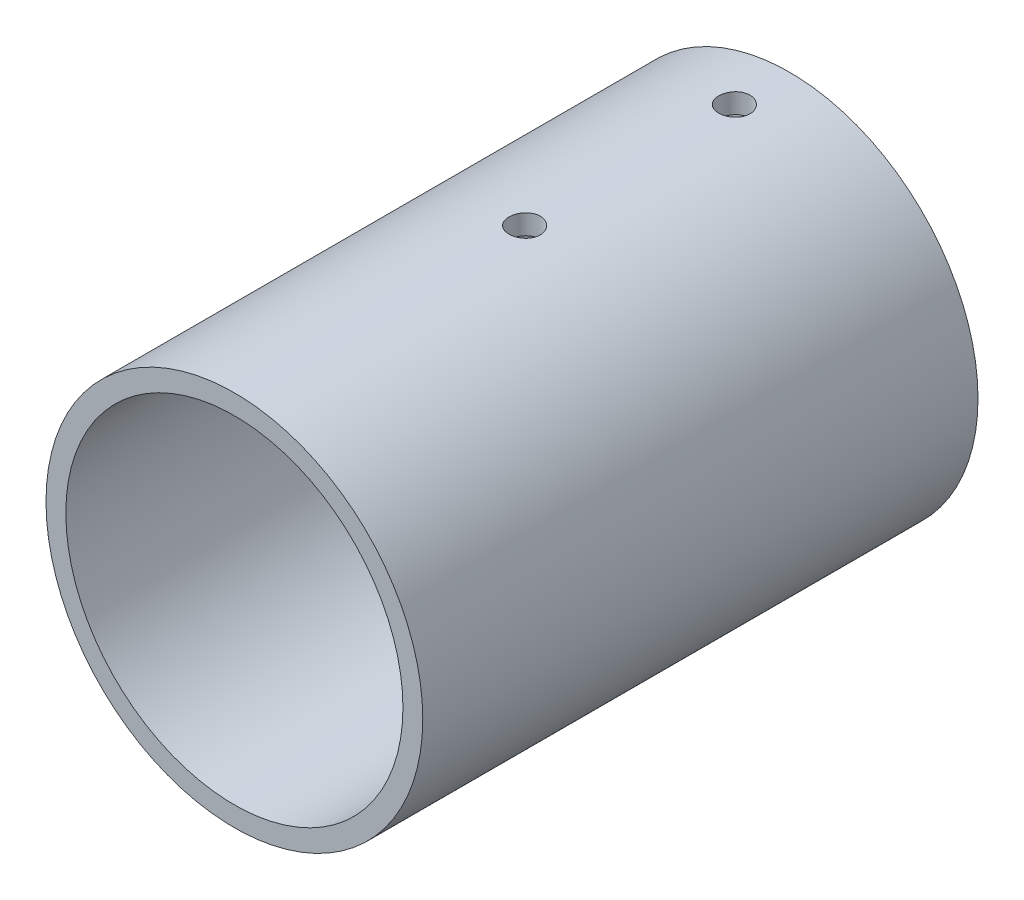
SolidWorks part; units mm, degrees
ref_plane "Front Plane" through (0, 0, 0) normal (0, 0, 1) x (1, 0, 0)
ref_plane "Top Plane" through (0, 0, 0) normal (0, 1, 0) x (1, 0, 0)
ref_plane "Right Plane" through (0, 0, 0) normal (1, 0, 0) x (0, 0, -1)
sketch "Sketch1" plane through (0, 0, 0) normal (0, 0, 1) x (1, 0, 0)
  circle A0 centre (0, 0) radius 60.325
  dimension "D1" = 120.65
extrude "Boss-Extrude1" add sketch "Sketch1" along normal blind 177.8
sketch "Sketch2" plane through (0, 0, 177.8) normal (0, 0, 1) x (1, 0, 0)
  circle A0 centre (0, 0) radius 31.75
  dimension "D1" = 63.5
extrude "Cut-Extrude1" cut sketch "Sketch2" against normal through all
sketch "Sketch3" plane through (0, 0, 177.8) normal (0, 0, 1) x (1, 0, 0)
  circle A0 centre (0, 0) radius 53.975
  dimension "D1" = 107.95
extrude "Cut-Extrude2" cut sketch "Sketch3" against normal blind 165.1
sketch "Sketch8" plane through (0, 0, 0) normal (0, 1, 0) x (1, 0, 0)
  circle A0 centre (0, -17.7) radius 5
  circle A1 centre (0, -84.85) radius 5
  point P4 (0, 0)
  dimension "D3" = 10
  dimension "D1" = 17.7
  dimension "D2" = 67.15
extrude "Cut-Extrude5" cut sketch "Sketch8" against normal through all both and the other way through all
